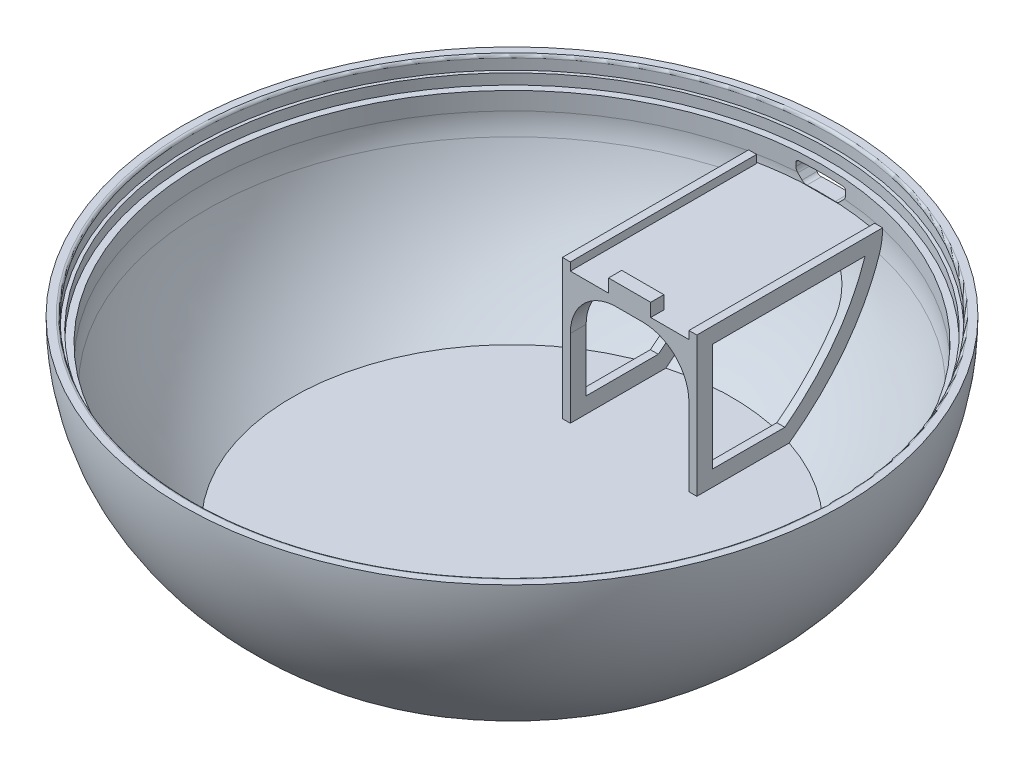
SolidWorks part; units mm, degrees
ref_plane "Plano frontal" through (0, 0, 0) normal (0, 0, 1) x (1, 0, 0)
ref_plane "Plano superior" through (0, 0, 0) normal (0, 1, 0) x (1, 0, 0)
ref_plane "Plano direito" through (0, 0, 0) normal (1, 0, 0) x (0, 0, -1)
sketch "Esboço1" plane through (0, 0, 0) normal (0, 0, 1) x (1, 0, 0)
  line L0 (0, 0) -> (0, -29.3333)
  line L1 (33.9935, -29.3333) -> (0, -29.3333)
  line L4 (0, 0) -> (50, 0)
  ellipse E0 centre (0, 0) end of major axis (-50, 0) minor radius 40 (33.9935, -29.3333) -> (50, 0) ccw
  dimension "D1" = 40
  dimension "D2" = 100
  dimension "D3" = 33.9935
revolve "Revolução1" add sketch "Esboço1" angle 360 about L0
shell "Casca1" thickness 2 removed face at (0, 0, 50)
sketch "Esboço7" plane through (0, 0, 0) normal (0, 1, 0) x (1, 0, 0)
  circle A0 centre (0, 0) radius 47
  circle A1 centre (0, 0) radius 48
  dimension "D1" = 94
extrude "Ressalto-extrusão3" add sketch "Esboço7" against normal up to next
sketch "Esboço9" plane through (0, 0, 0) normal (0, 1, 0) x (1, 0, 0)
  circle A0 centre (0, 0) radius 48.5
  dimension "D1" = 97
extrude "Corte-extrusão5" cut sketch "Esboço9" against normal blind 2
fillet "Filete3" radius 10 1 edges at (0, -7.7061, 47)
fillet "Filete4" radius 0.4 1 edges at (0, 0, 48.5)
fillet "Filete9" radius 6 1 edges at (0, -29.3333, 33.9935)
sketch "Esboço10" plane through (0, -2, 0) normal (0, 1, 0) x (1, 0, 0)
  circle A0 centre (0, 0) radius 48
  dimension "D1" = 96
extrude "Corte-extrusão6" cut sketch "Esboço10" against normal blind 1.6
sketch "Esboço15" plane through (0, 0, 0) normal (0, 0, 1) x (1, 0, 0)
  line L0 (0, -7.3333) -> (0, -4.7333) construction
  line L2 (-3.375, -4.7333) -> (3.375, -4.7333)
  line L3 (3.775, -5.1333) -> (3.775, -5.681)
  line L4 (3.4964, -6.3736) -> (2.8702, -7.0259)
  line L5 (2.1488, -7.3333) -> (-2.1488, -7.3333)
  line L6 (33.3248, -27.3333) -> (-33.3248, -27.3333) construction
  line L7 (-3.4964, -6.3736) -> (-2.8702, -7.0259)
  line L8 (-3.775, -5.1333) -> (-3.775, -5.681)
  arc A0 (2.8702, -7.0259) -> (2.1488, -7.3333) centre (2.1488, -6.3333) cw
  arc A1 (-2.8702, -7.0259) -> (-2.1488, -7.3333) centre (-2.1488, -6.3333) ccw
  arc A2 (3.775, -5.681) -> (3.4964, -6.3736) centre (2.775, -5.681) cw
  arc A3 (-3.4964, -6.3736) -> (-3.775, -5.681) centre (-2.775, -5.681) cw
  arc A4 (3.375, -4.7333) -> (3.775, -5.1333) centre (3.375, -5.1333) cw
  arc A5 (-3.775, -5.1333) -> (-3.375, -4.7333) centre (-3.375, -5.1333) cw
  point P14 (2.575, -7.3333)
  point P17 (-2.575, -7.3333)
  point P20 (3.775, -6.0833)
  point P23 (-3.775, -6.0833)
  point P26 (3.775, -4.7333)
  point P29 (-3.775, -4.7333)
  dimension "D6" = 1
  dimension "D7" = 0.4
  dimension "D1" = 7.55
  dimension "D2" = 2.6
  dimension "D3" = 1.35
  dimension "D4" = 5.15
  dimension "D5" = 20
extrude "Corte-extrusão9" cut sketch "Esboço15" against normal blind 62
ref_plane "Plano1" through (0, 0, -46.8482) normal (0, 0, -1) x (-1, 0, 0)
sketch "Esboço17" plane through (0, 0, -46.8482) normal (0, 0, -1) x (-1, 0, 0)
  line L0 (3.775, -5.681) -> (3.775, -5.1333) construction
  line L1 (10, -7.3333) -> (-10.4, -7.3333)
  line L2 (10, -7.3333) -> (10, -8.5333)
  line L3 (10, -8.5333) -> (-10.4, -8.5333)
  line L4 (-10.4, -7.3333) -> (-10.4, -8.5333)
  line L5 (-3.775, -5.1333) -> (-3.775, -5.681) construction
  line L7 (-3.375, -4.7333) -> (3.375, -4.7333) construction
  dimension "D1" = 1.2
  dimension "D2" = 6.225
  dimension "D3" = 20.4
  dimension "D4" = 2.6
  dimension "D5" = 6.625
extrude "Ressalto-extrusão4" add sketch "Esboço17" against normal blind 29.2
sketch "Esboço19" plane through (0, -8.5333, 0) normal (0, -1, 0) x (1, 0, 0)
  line L1 (-10, -17.6482) -> (-8.8, -17.6482)
  line L2 (-10, -17.6482) -> (-10, -45.9094)
  line L3 (-10, -45.9094) -> (-8.8, -45.9094)
  line L4 (-8.8, -17.6482) -> (-8.8, -45.9094)
  line L5 (10.4, -17.6482) -> (9.2, -17.6482)
  line L6 (10.4, -17.6482) -> (10.4, -45.831)
  line L7 (10.4, -45.831) -> (9.2, -45.831)
  line L8 (9.2, -17.6482) -> (9.2, -45.831)
  arc A0 (-10, -45.6631) -> (10.4, -45.5736) centre (0, 0) ccw construction
  dimension "D1" = 1.2
  dimension "D2" = 1.2
extrude "Ressalto-extrusão5" add sketch "Esboço19" along normal up to next and the other way blind 2.4
sketch "Esboço20" plane through (0, -7.3333, 0) normal (0, 1, 0) x (1, 0, 0)
  line L0 (-8.8, 17.6482) -> (9.2, 17.6482) construction
  line L1 (-3, 17.6482) -> (3.4, 17.6482)
  line L2 (-3, 17.6482) -> (-3, 19.6482)
  line L3 (-3, 19.6482) -> (3.4, 19.6482)
  line L4 (3.4, 17.6482) -> (3.4, 19.6482)
  line L5 (-10, 17.6482) -> (-10, 45.9094) construction
  point P6 (-3, 18.6482)
  dimension "D1" = 2
  dimension "D2" = 7
  dimension "D3" = 6.4
extrude "Ressalto-extrusão6" add sketch "Esboço20" along normal blind 2
fillet "Filete10" radius 7 2 edges at (9.2, -8.5333, -31.7396) (-8.8, -8.5333, -31.7788)
sketch "Esboço22" plane through (-10, 0, 0) normal (-1, 0, 0) x (0, 0, 1)
  line L4 (-30.9951, -24.9333) -> (-20.0482, -24.9333)
  line L5 (-20.0482, -24.9333) -> (-20.0482, -8.5333)
  line L6 (-20.0482, -8.5333) -> (-43.1747, -8.5333)
  line L7 (-43.1747, -8.5333) -> (-43.1747, -8.5333)
  line L8 (-31.789, -27.3333) -> (-17.6482, -27.3333)
  line L9 (-17.6482, -27.3333) -> (-17.6482, -6.1333)
  line L10 (-17.6482, -6.1333) -> (-45.9094, -6.1333)
  line L11 (-45.9094, -6.1333) -> (-45.9094, -6.8209)
  line L12 (-31.789, -27.3333) -> (-17.6482, -27.3333)
  line L13 (-17.6482, -27.3333) -> (-17.6482, -6.1333)
  line L14 (-17.6482, -6.1333) -> (-45.9094, -6.1333)
  line L15 (-45.9094, -6.1333) -> (-45.9094, -6.8209)
  spline S0 degree 1 poles (-43.1747, -8.5333) (-43.153, -8.6006) knots 0 0 1 1 construction
  spline S1 degree 1 poles (-43.153, -8.6006) (-30.9951, -24.9333) knots 0 0 1 1 construction
  spline S2 degree 3 poles (-3029.8638, 105.7128) (1378.8052, 270.2244) (-63.7694, 87.7577) (-40.427, -36.4503) (94.6861, -56.6147) (-423.7238, 2963.5881) knots -112.684195 -112.684195 -112.684195 -112.684195 0.5 0.5 33.980446 33.980446 33.980446 33.980446 only from (-45.9094, -6.8209) to (-45.4326, -9.351)
  spline S3 degree 3 poles (2457.4829, 1635.5331) (162.9448, 292.8705) (-84.0678, 61.0324) (-42.2579, -16.2752) (-41.2131, -17.87) (-39.4461, -20.1538) (-38.8282, -20.8907) (-37.5459, -22.3105) (-36.8803, -22.9948) (85.7189, -140.5061) (928.7106, 496.5601) (-1687.4677, -2483.0647) knots -11.064208 -11.064208 -11.064208 -11.064208 0.25 0.25 0.5 0.5 0.625 0.625 0.75 0.75 22.876083 22.876083 22.876083 22.876083 only from (-45.4326, -9.351) to (-31.789, -27.3333)
  spline S4 degree 3 poles (-45.9094, -6.8209) (-45.8862, -7.2477) (-45.8352, -7.6728) (-45.676, -8.5197) (-45.5675, -8.9413) (-45.4326, -9.351) knots 0 0 0 0 0.5 0.5 1 1 1 1
  spline S5 degree 3 poles (-45.4326, -9.351) (-44.8289, -11.1851) (-44.0656, -12.9326) (-42.2579, -16.2752) (-41.2131, -17.87) (-39.4461, -20.1538) (-38.8282, -20.8907) (-37.5459, -22.3105) (-36.8803, -22.9948) (-34.8141, -24.9752) (-33.3446, -26.1992) (-31.789, -27.3333) knots 0 0 0 0 0.25 0.25 0.5 0.5 0.625 0.625 0.75 0.75 1 1 1 1
  spline S6 degree 3 poles (-43.1747, -8.5333) (-43.1676, -8.5558) (-43.1603, -8.5782) (-43.153, -8.6006) knots 0.963752 0.963752 0.963752 0.963752 1 1 1 1
  spline S7 degree 3 poles (-43.153, -8.6006) (-42.0888, -11.8334) (-38.816, -17.9031) (-33.7546, -22.8432) (-30.9951, -24.9333) knots 0 0 0 0 0.482313 0.964625 0.964625 0.964625 0.964625
  dimension "D1" = 0
  dimension "D2" = 2.4
extrude "Corte-extrusão11" cut sketch "Esboço22" against normal up to surface (20.4 mm away) contours L6 L7 S6 S7 L4 L5 up to face at (10.4, -12.9495, -31.1706)
sketch "Esboço24" plane through (0, 0, 0) normal (0, 0, 1) x (1, 0, 0)
  line L0 (9.2, -27.3333) -> (10.4, -27.3333) construction
  circle A0 centre (0, -13.3333) radius 2
  dimension "D1" = 4
  dimension "D2" = 14
extrude "Corte-extrusão12" cut sketch "Esboço24" against normal up to next
